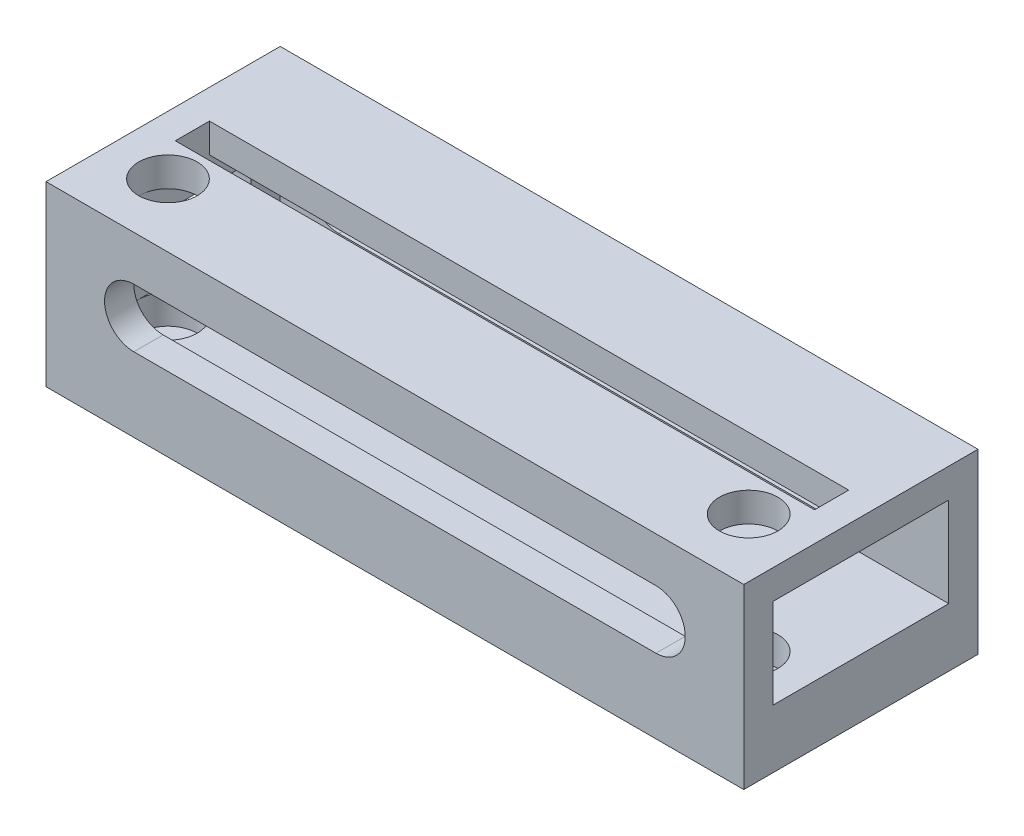
SolidWorks part; units mm, degrees
ref_plane "Front Plane" through (0, 0, 0) normal (0, 0, 1) x (1, 0, 0)
ref_plane "Top Plane" through (0, 0, 0) normal (0, 1, 0) x (1, 0, 0)
ref_plane "Right Plane" through (0, 0, 0) normal (1, 0, 0) x (0, 0, -1)
sketch "Sketch1" plane through (0, 0, 0) normal (0, 1, 0) x (1, 0, 0)
  line L1 (-32.75, -4.5) -> (32.75, -4.5)
  line L2 (-32.75, -4.5) -> (-32.75, 4.5)
  line L3 (-32.75, 4.5) -> (32.75, 4.5)
  line L4 (32.75, -4.5) -> (32.75, 4.5)
  line L5 (-32.75, -4.5) -> (32.75, 4.5) construction
  line L6 (-32.75, 4.5) -> (32.75, -4.5) construction
  circle A0 centre (-29.75, 0) radius 0.9984
  circle A1 centre (29.75, 0) radius 1.2431
  point P0 (0, 0)
  dimension "D1" = 9
  dimension "D2" = 65.5
  dimension "D3" = 29.75
  dimension "D4" = 59.5
extrude "Boss-Extrude1" add sketch "Sketch1" along normal blind 6
sketch "Sketch3" plane through (0, 0, -4.5) normal (0, 0, -1) x (-1, 0, 0)
  line L1 (-32.75, 6) -> (32.75, 6)
  line L2 (-32.75, 6) -> (-32.75, 0)
  line L3 (-32.75, 0) -> (32.75, 0)
  line L4 (32.75, 6) -> (32.75, 0)
extrude "Boss-Extrude2" add sketch "Sketch3" along normal blind 10
sketch "Sketch4" plane through (0, 0, 4.5) normal (0, 0, 1) x (1, 0, 0)
  line L1 (-32.75, 6) -> (32.75, 6)
  line L2 (-32.75, 6) -> (-32.75, 0)
  line L3 (-32.75, 0) -> (32.75, 0)
  line L4 (32.75, 6) -> (32.75, 0)
extrude "Boss-Extrude3" add sketch "Sketch4" along normal blind 2
sketch "Sketch5" plane through (0, 6, 0) normal (0, 1, 0) x (1, 0, 0)
  line L5 (-32.75, 14.5) -> (-32.75, -6.5) construction
  line L6 (32.75, -6.5) -> (-32.75, -6.5)
  line L7 (32.75, -6.5) -> (32.75, -3.5)
  line L8 (32.75, -3.5) -> (-32.75, -3.5)
  line L9 (-32.75, -6.5) -> (-32.75, -3.5)
  dimension "D1" = 3
extrude "Boss-Extrude4" add sketch "Sketch5" along normal blind 9.2
sketch "Sketch7" plane through (-32.75, 0, 0) normal (-1, 0, 0) x (0, 0, 1)
  line L1 (6.5, 15.2) -> (-14.5, 15.2)
  line L2 (6.5, 15.2) -> (6.5, 0)
  line L3 (6.5, 0) -> (-14.5, 0)
  line L4 (-14.5, 15.2) -> (-14.5, 0)
extrude "Boss-Extrude6" add sketch "Sketch7" along normal blind 3
sketch "Sketch12" plane through (0, 0, -14.5) normal (0, 0, -1) x (-1, 0, 0)
  line L0 (-32.75, 15.2) -> (-32.75, 6) construction
  line L1 (-32.75, 15.2) -> (35.75, 15.2)
  line L2 (-32.75, 15.2) -> (-32.75, 0)
  line L3 (-32.75, 0) -> (35.75, 0)
  line L4 (35.75, 15.2) -> (35.75, 0)
  dimension "D1" = 0
extrude "Boss-Extrude10" add sketch "Sketch12" along normal blind 3
sketch "Sketch13" plane through (32.75, 0, 0) normal (1, 0, 0) x (0, 0, -1)
  line L0 (17.5, 15.2) -> (17.5, 0) construction
  line L1 (-6.5, 15.2) -> (17.5, 15.2)
  line L2 (-6.5, 15.2) -> (-6.5, 12.45)
  line L3 (-6.5, 12.45) -> (17.5, 12.45)
  line L4 (17.5, 15.2) -> (17.5, 12.45)
  line L5 (-3.5, 15.2) -> (-3.5, 6) construction
  line L6 (17.5, 8.75) -> (-6.5, 8.75)
  line L7 (17.5, 8.75) -> (17.5, 0)
  line L8 (17.5, 0) -> (-6.5, 0)
  line L9 (-6.5, 8.75) -> (-6.5, 0)
  line L10 (-6.5, 15.2) -> (-0.5, 15.2)
  line L11 (-6.5, 15.2) -> (-6.5, 8.75)
  line L12 (-6.5, 8.75) -> (-0.5, 8.75)
  line L13 (-0.5, 15.2) -> (-0.5, 8.75)
  line L14 (17.5, 15.2) -> (11.5, 15.2)
  line L15 (17.5, 15.2) -> (17.5, 8.75)
  line L16 (17.5, 8.75) -> (11.5, 8.75)
  line L17 (11.5, 15.2) -> (11.5, 8.75)
  line L18 (14.5, 15.2) -> (14.5, 6) construction
  line L19 (-3.5, 6) -> (14.5, 6) construction
  line M8 (14.5, 6) -> (-3.5, 6)
  line M9 (-3.5, 6) -> (-3.5, 15.2)
  line M11 (-6.5, 15.2) -> (-6.5, 0)
  line M12 (-6.5, 0) -> (17.5, 0)
  line M13 (17.5, 0) -> (17.5, 15.2)
  line M14 (17.5, 15.2) -> (14.5, 15.2)
  line M15 (14.5, 15.2) -> (14.5, 6)
  line M16 (14.5, 6) -> (-3.5, 6)
  dimension "D1" = 3
  dimension "D2" = 3
  dimension "D3" = 2.75
  dimension "D4" = 2.75
extrude "Boss-Extrude11" add sketch "Sketch13" along normal blind 3 contours L13 L1 L3 M9 | L3 M11 M9 | L6 L3 M9 M11 | L13 L3 L6 M9 | L17 L1 L13 L3 | L1 L17 L3 M15 | L3 M15 M13 M14 | L3 L17 L6 M15 | L6 L3 M13 M15 | L6 M15 M9 M8 M16 | L6 M13 M15 M16 M8 M9 M11 M12 region at (32.75, 13.825, 5) region at (32.75, 13.825, 2) region at (32.75, 10.6, 5) region at (32.75, 13.825, -5.5) region at (32.75, 10.6, 2) region at (32.75, 3.4498, -5.5) region at (32.75, 13.825, -13) region at (32.75, 7.375, -5.5) region at (32.75, 13.825, -16) region at (32.75, 10.6, -13) region at (32.75, 10.6, -16)
sketch "Sketch6" plane through (0, 0, 6.5) normal (0, 0, 1) x (1, 0, 0)
  line L5 (-26.75, 13.6) -> (26.75, 13.6)
  line L6 (26.75, 13.6) -> (26.75, 7.6)
  line L7 (26.75, 7.6) -> (-26.75, 7.6)
  line L8 (-26.75, 7.6) -> (-26.75, 13.6)
  line L12 (-35.75, 0) -> (-35.75, 15.2) construction
  line L14 (35.75, 15.2) -> (35.75, 0) construction
  circle A0 centre (-26.75, 10.6) radius 3
  circle A1 centre (26.75, 10.6) radius 3
  dimension "D1" = 6
  dimension "D4" = 6
  dimension "D2" = 9
  dimension "D5" = 9
extrude "Cut-Extrude2" cut sketch "Sketch6" against normal through all contours L8 A0 | L8 A0 | L6 A1 | L6 A1 | A1 L5 A0 L7 region at (-25.4768, 10.6, 6.5) region at (0, 10.6, 6.5) region at (-28.0232, 10.6, 6.5) region at (28.0232, 10.6, 6.5) region at (25.4768, 10.6, 6.5)
sketch "Sketch11" plane through (-35.75, 0, 0) normal (-1, 0, 0) x (0, 0, 1)
  line L0 (6.5, 0) -> (6.5, 15.2) construction
  line L1 (-14.5, 15.2) -> (3.5, 15.2)
  line L2 (-14.5, 15.2) -> (-14.5, 6)
  line L3 (-14.5, 6) -> (3.5, 6)
  line L4 (3.5, 15.2) -> (3.5, 6)
  line L6 (-17.5, 0) -> (6.5, 0) construction
  line L8 (-17.5, 0) -> (-17.5, 15.2) construction
  dimension "D1" = 3
  dimension "D3" = 6
  dimension "D4" = 3
extrude "Cut-Extrude4" cut sketch "Sketch11" against normal blind 3
sketch "Sketch14" plane through (0, 15.2, 0) normal (0, 1, 0) x (1, 0, 0)
  line L1 (-35.75, 17.5) -> (35.75, 17.5)
  line L2 (-35.75, 17.5) -> (-35.75, -6.5)
  line L3 (-35.75, -6.5) -> (35.75, -6.5)
  line L4 (35.75, 17.5) -> (35.75, -6.5)
extrude "Boss-Extrude12" add sketch "Sketch14" along normal blind 3
sketch "Sketch15" plane through (0, 18.2, 0) normal (0, 1, 0) x (1, 0, 0)
  line L0 (35.75, -6.5) -> (35.75, 17.5) construction
  line L1 (-32.75, 7.25) -> (32.75, 7.25)
  line L2 (-32.75, 7.25) -> (-32.75, 3.75)
  line L3 (-32.75, 3.75) -> (32.75, 3.75)
  line L4 (32.75, 7.25) -> (32.75, 3.75)
  line L5 (-35.75, 17.5) -> (-35.75, -6.5) construction
  line L6 (-35.75, -6.5) -> (35.75, -6.5) construction
  dimension "D1" = 3
  dimension "D2" = 3
  dimension "D3" = 10.25
  dimension "D4" = 3.5
extrude "Cut-Extrude5" cut sketch "Sketch15" against normal blind 3
sketch "Sketch16" plane through (0, 18.2, 0) normal (0, 1, 0) x (1, 0, 0)
  circle A2 centre (-29.75, 0) radius 3
  circle A3 centre (29.75, 0) radius 3
  dimension "D1" = 6
  dimension "D2" = 6
extrude "Cut-Extrude6" cut sketch "Sketch16" against normal offset from surface (15.2 mm away) 3 up to face at (29.75, 6, 1.2431) offset beyond the face yes
mirror "Mirror10" about plane through (35.75, 0, 0) normal (1, 0, 0) of "Boss-Extrude1", "Boss-Extrude2", "Boss-Extrude3", "Boss-Extrude4", "Boss-Extrude6", "Boss-Extrude10", "Boss-Extrude11", "Cut-Extrude2", "Cut-Extrude4", "Boss-Extrude12", "Cut-Extrude5", "Cut-Extrude6"
sketch "Sketch17" plane through (0, 18.2, 0) normal (0, 1, 0) x (1, 0, 0)
  line L0 (-35.75, -6.5) -> (107.25, -6.5) construction
  line L1 (-35.75, 17.5) -> (35.75, 17.5)
  line L2 (-35.75, 17.5) -> (-35.75, -6.5)
  line L3 (-35.75, -6.5) -> (35.75, -6.5)
  line L4 (35.75, 17.5) -> (35.75, -6.5)
  line L5 (38.75, 3.75) -> (38.75, 7.25) construction
  dimension "D1" = 3
extrude "Cut-Extrude7" cut sketch "Sketch17" against normal through all
equation "\"D4@Sketch6\"= \"D1@Sketch6\""
